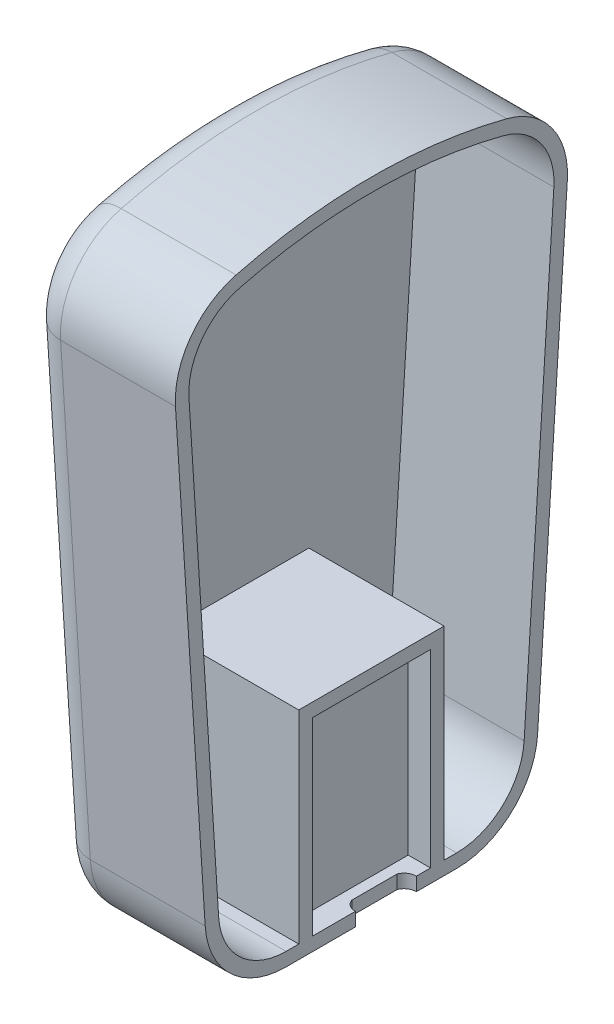
SolidWorks part; units mm, degrees
ref_plane "Front Plane" through (0, 0, 0) normal (0, 0, 1) x (1, 0, 0)
ref_plane "Top Plane" through (0, 0, 0) normal (0, 1, 0) x (1, 0, 0)
ref_plane "Right Plane" through (0, 0, 0) normal (1, 0, 0) x (0, 0, -1)
sketch "Sketch2" plane through (0, 0, 0) normal (1, 0, 0) x (0, 0, -1)
  line L0 (0, 0) -> (0, 39.94) construction
  line L1 (0, 39.94) -> (0, -45.06) construction
  line L2 (27.5, 39.94) -> (-27.5, 39.94) construction
  line L3 (15, -45.06) -> (-15, -45.06) construction
  line L4 (-6.5405, 39.94) -> (-6.5405, -14.06) construction
  line L5 (22.5, -14.06) -> (-22.5, -14.06) construction
  line L6 (-27.0012, 32.141) -> (-22.6028, -36.6303)
  line L7 (27.0012, 32.141) -> (22.6028, -36.6303)
  line L8 (-12.6232, -45.992) -> (12.6232, -45.992)
  line L9 (0, 39.94) -> (-22.5, 39.94) construction
  arc A0 (-19.5202, 42.4621) -> (19.5202, 42.4621) centre (0, -33.185) cw
  arc A1 (-19.5202, 42.4621) -> (-27.0012, 32.141) centre (-17.0216, 32.7793) ccw
  arc A2 (19.5202, 42.4621) -> (27.0012, 32.141) centre (17.0216, 32.7793) cw
  arc A3 (-12.6232, -45.992) -> (-22.6028, -36.6303) centre (-12.6232, -35.992) cw
  arc A4 (22.6028, -36.6303) -> (12.6232, -45.992) centre (12.6232, -35.992) cw
  point P12 (0, -14.06)
  point P14 (0, 44.94)
  point P26 (-22.0041, -45.992)
  point P29 (22.0041, -45.992)
  point P30 (0, 0)
  point P31 (0, 0)
  dimension "D6" = 5
  dimension "D7" = 10
  dimension "D8" = 10
  dimension "D9" = 10
  dimension "D10" = 10
  dimension "D1" = 85
  dimension "D2" = 27.5
  dimension "D3" = 15
  dimension "D4" = 54
  dimension "D5" = 22.5
extrude "Boss-Extrude1" add sketch "Sketch2" along normal blind 20
shell "Shell4" thickness 2 removed face at (20, -1.852, 0) outward yes
fillet "Fillet2" radius 5 8 edges at (-2, 46.94, 0) (-2, 39.8218, -26.7377) (-2, -2.3723, -26.7979) (-2, -44.7439, -20.8333) (-2, -47.992, 0) (-2, -44.7439, 20.8333) (-2, -2.3723, 26.7979) (-2, 39.8218, 26.7377)
sketch "Sketch3" plane through (0, 0, 0) normal (1, 0, 0) x (0, 0, -1)
  line L0 (-12.6232, -45.992) -> (12.6232, -45.992) construction
  line L1 (10.75, -45.992) -> (-10.75, -45.992)
  line L2 (10.75, -45.992) -> (10.75, -15.992)
  line L3 (10.75, -15.992) -> (-10.75, -15.992)
  line L4 (-10.75, -45.992) -> (-10.75, -15.992)
  line L5 (10.75, -45.992) -> (-10.75, -15.992) construction
  line L6 (10.75, -15.992) -> (-10.75, -45.992) construction
  line L7 (0, 55) -> (0, -55) construction
  point P0 (0, -30.992)
  dimension "D1" = 0
  dimension "D2" = 30
  dimension "D3" = 21.5
  dimension "D4" = 0
extrude "Boss-Extrude2" add sketch "Sketch3" along normal blind 20
sketch "Sketch4" plane through (20, 0, 0) normal (1, 0, 0) x (0, 0, -1)
  line L0 (10.75, -15.992) -> (-10.75, -15.992) construction
  line L1 (-8.75, -17.992) -> (8.75, -17.992)
  line L2 (-8.75, -17.992) -> (-8.75, -45.992)
  line L3 (-8.75, -45.992) -> (8.75, -45.992)
  line L4 (8.75, -17.992) -> (8.75, -45.992)
  line L5 (-10.75, -15.992) -> (-10.75, -45.992) construction
  line L6 (10.75, -15.992) -> (10.75, -45.992) construction
  line L7 (-12.6232, -47.992) -> (12.6232, -47.992) construction
  dimension "D1" = 2
  dimension "D2" = 2
  dimension "D3" = 2
  dimension "D4" = 2
extrude "Cut-Extrude1" cut sketch "Sketch4" against normal blind 3.3
sketch "Sketch5" plane through (0, -47.992, 0) normal (0, -1, 0) x (1, 0, 0)
  line L0 (20, 2.3518) -> (20, -6.6482)
  line L1 (20, 12.6232) -> (20, -12.6232) construction
  line L2 (20, -2.1477) -> (18.3, -2.1477) construction
  line L3 (18.3, -5.4927) -> (18.3, 1.1973)
  arc A0 (18.3, 1.1973) -> (20, 2.3518) centre (19.9047, 0.6632) cw
  arc A1 (18.3, -5.4927) -> (20, -6.6482) centre (19.9409, -4.9068) ccw
  point P7 (20, -2.1482)
  dimension "D1" = 9
  dimension "D2" = 5.975
  dimension "D3" = 1.7
  dimension "D4" = 0.001
  dimension "D5" = 3.345
extrude "Cut-Extrude2" cut sketch "Sketch5" against normal up to surface (2 mm away) up to face at (18.35, -45.992, 0)
